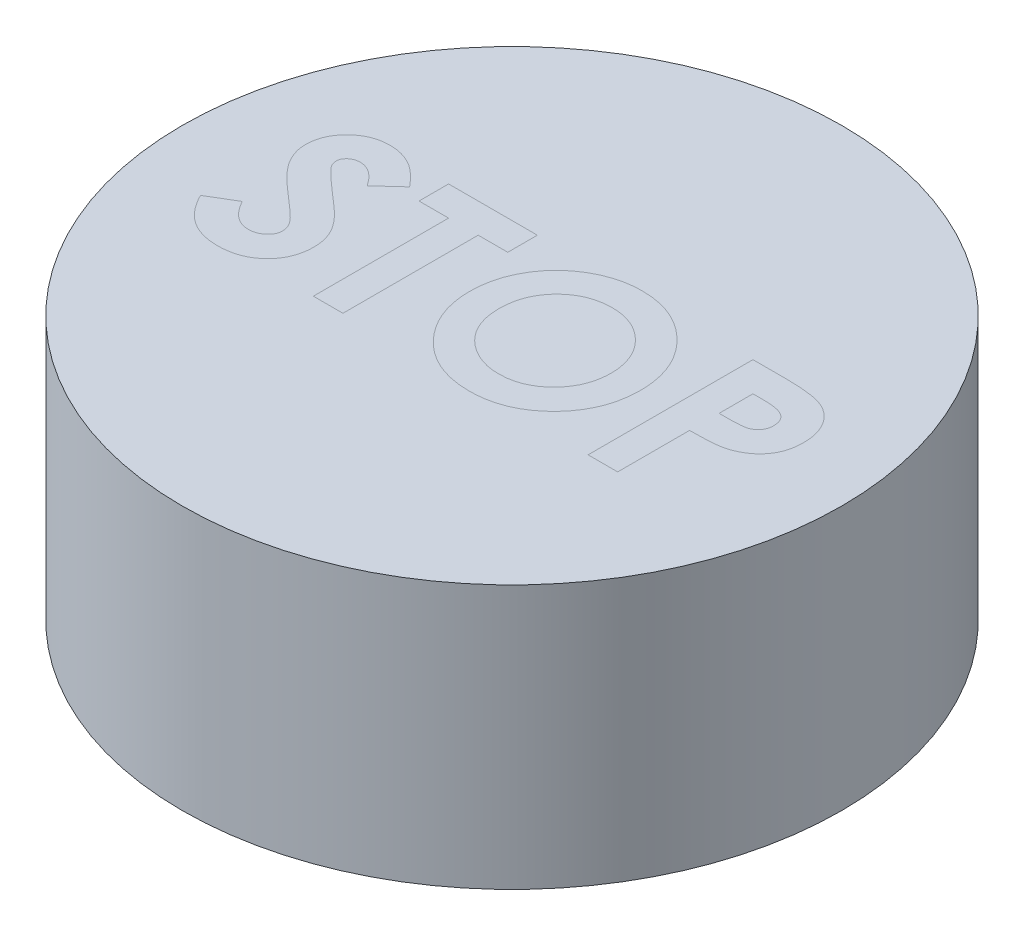
SolidWorks part; units mm, degrees
ref_plane "Front Plane" through (0, 0, 0) normal (0, 0, 1) x (1, 0, 0)
ref_plane "Top Plane" through (0, 0, 0) normal (0, 1, 0) x (1, 0, 0)
ref_plane "Right Plane" through (0, 0, 0) normal (1, 0, 0) x (0, 0, -1)
sketch "Sketch3" plane through (0, 0, 0) normal (0, 1, 0) x (1, 0, 0)
  line L1 (1.075, -1.575) -> (-1.075, -1.575)
  line L2 (1.075, -1.575) -> (1.075, 1.575)
  line L3 (1.075, 1.575) -> (-1.075, 1.575)
  line L4 (-1.075, -1.575) -> (-1.075, 1.575)
  line L5 (1.075, -1.575) -> (-1.075, 1.575) construction
  line L6 (1.075, 1.575) -> (-1.075, -1.575) construction
  circle A0 centre (0, 0) radius 10
  point P0 (0, 0)
  dimension "D3" = 20
  dimension "D1" = 2.15
  dimension "D2" = 3.15
extrude "Boss-Extrude1" add sketch "Sketch3" against normal blind 3
sketch "Sketch4" plane through (0, 0, 0) normal (0, 1, 0) x (1, 0, 0)
  circle A1 centre (0, 0) radius 10
  circle A2 centre (0, 0) radius 10
  dimension "D1" = 0
extrude "Boss-Extrude2" add sketch "Sketch4" along normal blind 5
sketch "Sketch5" plane through (0, 0, 0) normal (0, 1, 0) x (1, 0, 0)
  line L0 (-9.6825, -2.5) -> (9.6825, -2.5) construction
  line L1 (9.6825, -2.5) -> (9.6825, 2.5) construction
  circle A0 centre (0, 0) radius 10 construction
  text T0 "STOP\r\n" font "Century Gothic" height 5
  dimension "D1" = 5
extrude "Cut-Extrude1" cut sketch "Sketch5" against normal blind 0.4 and the other way through all from surface starting at face at (0, 5, 10)
extrude "Boss-Extrude3" add sketch "Sketch5<2>" against normal blind 0.4 from surface separate body starting at face at (-6.2494, 5, -0.1249)
sketch "Sketch5<2>" plane through (0, 0, 0) normal (0, 1, 0) x (1, 0, 0) same geometry as "Sketch5"
equation "\"m3 hole\"= 3.2"
equation "\"m4 hole\"= 4.2"
equation "\"m5 hole\"= 5.2"
equation "\"m6 hole\"= 6.2"
equation "\"m8 hole\"= 8.2"
equation "\"m3 tapped\"= 2.5"
equation "\"m4 tapped\"= 3.3"
equation "\"m5 tapped\"= 4.2"
equation "\"m6 tapped\"= 5"
equation "\"m8 tapped\"= 6.8"
